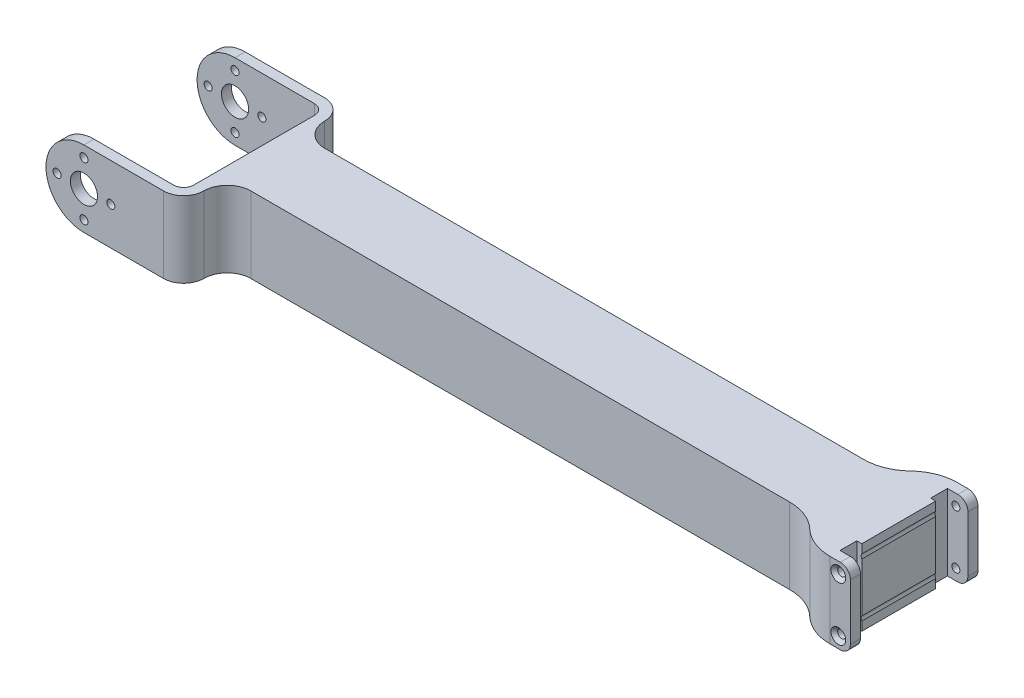
SolidWorks part; units mm, degrees
ref_plane "Front" through (0, 0, 0) normal (0, 0, 1) x (1, 0, 0)
ref_plane "Top" through (0, 0, 0) normal (0, 1, 0) x (1, 0, 0)
ref_plane "Right" through (0, 0, 0) normal (1, 0, 0) x (0, 0, -1)
sketch "Sketch4" plane through (0, 0, 0) normal (0, 1, 0) x (1, 0, 0)
  line L0 (0, -21) -> (0, -24)
  line L5 (0, -24) -> (35, -24)
  line L7 (48, -11) -> (230, -11)
  line L8 (230, -11) -> (230, 0)
  line L9 (230, 0) -> (38, 0)
  line L11 (35, -21) -> (0, -21)
  line L12 (38, -18) -> (38, 0)
  arc A0 (35, -21) -> (38, -18) centre (35, -18) ccw
  arc A2 (35, -24) -> (41, -18) centre (35, -18) ccw
  arc A4 (41, -18) -> (48, -11) centre (48, -18) cw
  point P11 (0, -22.5)
  dimension "D4" = 3
  dimension "D1" = 21
  dimension "D2" = 35
  dimension "D3" = 3
  dimension "D5" = 3
  dimension "D6" = 11
  dimension "D7" = 230
extrude "Boss-Extrude3" add sketch "Sketch4" along normal blind 22.6
fillet "Fillet2" radius 11.3 2 edges at (0, 0, 22.5) (0, 22.6, 22.5)
mirror "Mirror3" about plane through (0, 0, 0) normal (0, 0, 1) of bodies 120
sketch "Sketch5" plane through (0, 0, 0) normal (0, 1, 0) x (1, 0, 0)
  line L0 (208.5, 11) -> (228.5, 11)
  line L1 (48, 11) -> (230, 11) construction
  line L2 (228.5, 11) -> (228.5, 16)
  line L3 (228.5, 16) -> (234.6, 16)
  line L4 (234.6, 16) -> (234.6, 19)
  line L5 (234.6, 19) -> (228.5, 19)
  line L6 (230, -11) -> (230, 11) construction
  arc A0 (228.5, 19) -> (218.5, 15) centre (228.5, 4.5) ccw
  arc A1 (218.5, 15) -> (208.5, 11) centre (208.5, 25.5) cw
  dimension "D1" = 6.1
  dimension "D2" = 1.5
  dimension "D3" = 5
  dimension "D4" = 3
  dimension "D5" = 20
extrude "Boss-Extrude4" add sketch "Sketch5" along normal through all
hole_wizard "CSK for M2 Countersunk Flat Head Screw1" positions "3DSketch1" profile "Sketch6" countersink size "M2" standard "ISO" end condition through all
sketch3d "3DSketch1"
  line L1 (228.5, 22.6, -19) -> (228.5, 0, -19) construction
  line L2 (234.6, 11.3, -19) -> (228.5, 11.3, -19) construction
  line L3 (234.6, 22.6, -19) -> (234.6, 0, -19) construction
  point P0 (231, 3.3, -19)
  point P2 (231, 19.3, -19)
  dimension "D1" = 2.5
  dimension "D2" = 16
  dimension "D3" = 8
sketch "Sketch6" plane through (231, 3.3, -19) normal (1, 0, 0) x (0, 1, 0)
  line L0 (0, 0) -> (0, 43)
  line L1 (0, 43) -> (1.2, 43)
  line L2 (1.2, 43) -> (1.2, 1)
  line L3 (1.2, 1) -> (2.2, 0)
  line L5 (2.2, 0) -> (0, 0)
  line L6 (-1.2, 1) -> (-2.2, 0) construction
  line L11 (0, -6.35) -> (0, 107.95) construction
  dimension "Thru Hole Dia." = 2.4
  dimension "Thru Hole Depth" = 43
  dimension "Near C'Sink Dia." = 4.4
  dimension "Near C'Sink Angle" = 90
fillet "Fillet3" radius 3 2 edges at (234.6, 22.6, -17.5) (234.6, 0, -17.5)
mirror "Mirror4" about plane through (0, 0, 0) normal (0, 0, 1) of "Fillet3", "CSK for M2 Countersunk Flat Head Screw1", "Boss-Extrude4"
hole_wizard "M2 Clearance Hole1" positions "3DSketch5" profile "Sketch12" hole size "M2" standard "ISO" end condition up to next
sketch3d "3DSketch5"
  line L0 (3.3, 11.3, 24) -> (11.3, 11.3, 24) construction
  line L1 (11.3, 11.3, 21) -> (11.3, 11.3, 24) construction
  point P0 (3.3, 11.3, 24)
  dimension "D1" = 8
sketch "Sketch12" plane through (3.3, 11.3, 24) normal (1, 0, 0) x (0, -1, 0)
  line L0 (0, 0) -> (0, 3)
  line L1 (0, 3) -> (1.2, 3)
  line L2 (1.2, 3) -> (1.2, 0)
  line L5 (1.2, 0) -> (0, 0)
  line L11 (0, -6.35) -> (0, 107.95) construction
  dimension "Thru Hole Dia." = 2.4
  dimension "Thru Hole Depth" = 3
pattern_circular "CirPattern1" count 4 over 360 about axis through (11.3, 11.3, 18) along (0, 0, -1) of "M2 Clearance Hole1" reverse direction yes
hole_wizard "Ø8.1 (8.1) Diameter Hole1" positions "3DSketch4" profile "Sketch8" hole size "Ø8.1" standard "ISO" end condition up to next
sketch3d "3DSketch4"
  line L1 (11.3, 11.3, -24) -> (11.3, 11.3, -21) construction
  point P5 (11.3, 11.3, -24)
sketch "Sketch8" plane through (11.3, 11.3, -24) normal (1, 0, 0) x (0, 1, 0)
  line L0 (0, 0) -> (0, 3)
  line L1 (0, 3) -> (4.05, 3)
  line L2 (4.05, 3) -> (4.05, 0)
  line L5 (4.05, 0) -> (0, 0)
  line L11 (0, -6.35) -> (0, 107.95) construction
  dimension "Thru Hole Dia." = 8.1
  dimension "Thru Hole Depth" = 3
hole_wizard "Ø8.1 (8.1) Diameter Hole2" positions "3DSketch6" profile "Sketch13" hole size "Ø8.1" standard "ISO" end condition up to next
sketch3d "3DSketch6"
  line L0 (11.3, 11.3, 21) -> (11.3, 11.3, 24) construction
  point P0 (11.3, 11.3, 24)
sketch "Sketch13" plane through (11.3, 11.3, 24) normal (1, 0, 0) x (0, -1, 0)
  line L0 (0, 0) -> (0, 3)
  line L1 (0, 3) -> (4.05, 3)
  line L2 (4.05, 3) -> (4.05, 0)
  line L5 (4.05, 0) -> (0, 0)
  line L11 (0, -6.35) -> (0, 107.95) construction
  dimension "Thru Hole Dia." = 8.1
  dimension "Thru Hole Depth" = 3
hole_wizard "M2 Clearance Hole2" positions "3DSketch7" profile "Sketch14" hole size "M2" standard "ISO" end condition up to next
sketch3d "3DSketch7"
  line L0 (3.3, 11.3, -24) -> (11.3, 11.3, -24) construction
  line L1 (11.3, 11.3, -24) -> (11.3, 11.3, -21) construction
  line L2 (11.3, 11.3, -21) -> (11.3, 11.3, -24) construction
  point P0 (3.3, 11.3, -24)
  dimension "D1" = 8
sketch "Sketch14" plane through (3.3, 11.3, -24) normal (1, 0, 0) x (0, 1, 0)
  line L0 (0, 0) -> (0, 3)
  line L1 (0, 3) -> (1.2, 3)
  line L2 (1.2, 3) -> (1.2, 0)
  line L5 (1.2, 0) -> (0, 0)
  line L11 (0, -6.35) -> (0, 107.95) construction
  dimension "Thru Hole Dia." = 2.4
  dimension "Thru Hole Depth" = 3
pattern_circular "CirPattern2" count 4 over 360 about axis through (11.3, 11.3, -21) along (0, 0, -1) of "M2 Clearance Hole2" reverse direction yes
